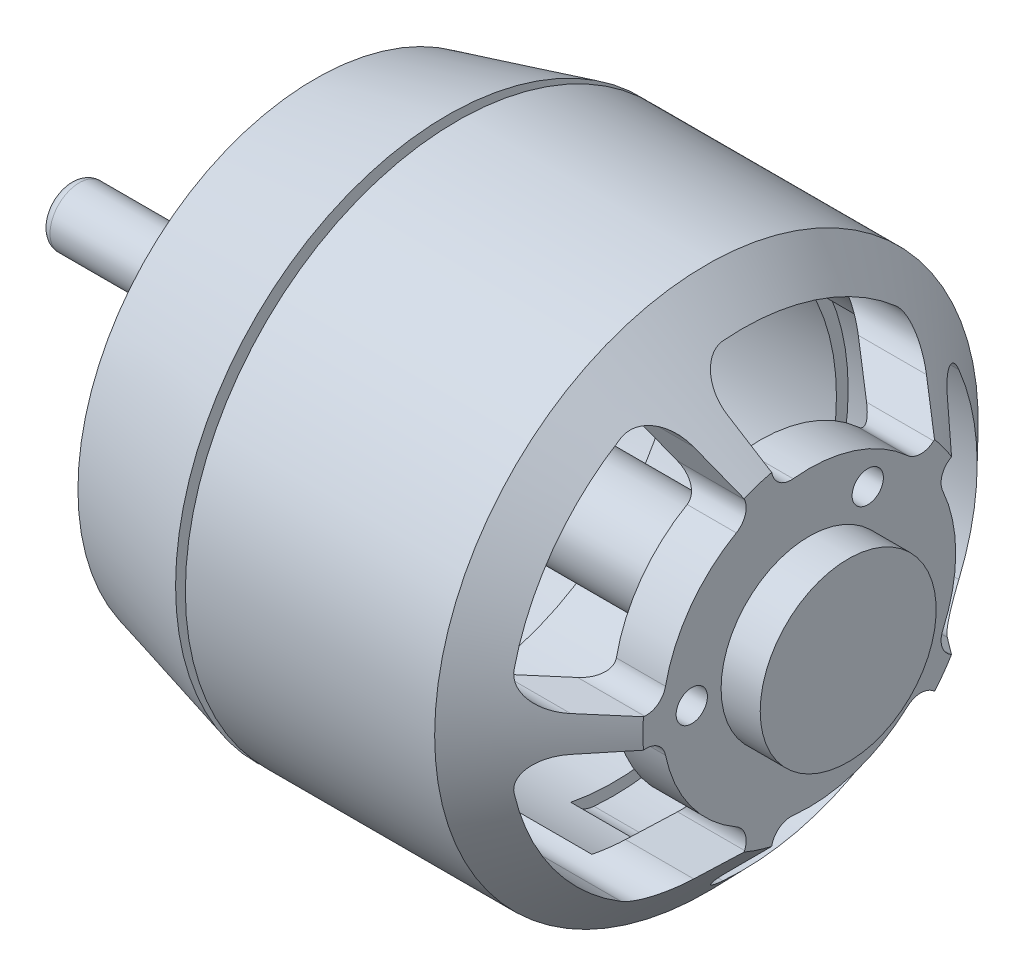
SolidWorks part; units mm, degrees
ref_plane "Front Plane" through (0, 0, 0) normal (0, 0, 1) x (1, 0, 0)
ref_plane "Top Plane" through (0, 0, 0) normal (0, 1, 0) x (1, 0, 0)
ref_plane "Right Plane" through (0, 0, 0) normal (1, 0, 0) x (0, 0, -1)
sketch "Sketch1" plane through (0, 0, 0) normal (0, 1, 0) x (1, 0, 0)
  line L0 (0, 0) -> (27.75, 0)
  line L1 (27.75, 0) -> (27.75, -4.5)
  line L2 (27.75, -4.5) -> (25.75, -4.5)
  line L3 (25.75, -4.5) -> (25.75, -8.5)
  line L4 (7.25, -13.9) -> (0, -12)
  line L5 (7.25, -12.9) -> (2, -11.5241)
  line L6 (7.75, -13.9) -> (20.5, -13.9)
  line L7 (20.5, -13.9) -> (25.75, -8.5)
  line L9 (0, -12) -> (0, -1.5)
  line L10 (7.75, -13.9) -> (7.75, -11.4)
  line L12 (23.25, -2.5) -> (23.25, -7.485)
  line L13 (19.4438, -11.4) -> (23.25, -7.485)
  line L14 (7.75, -11.4) -> (19.4438, -11.4)
  line L17 (2, -2.5) -> (23.25, -2.5)
  line L20 (7.25, -13.9) -> (7.25, -12.9)
  line L21 (2, -2.5) -> (2, -11.5241)
  line L22 (0, 0) -> (-12.07, 0)
  line L23 (-12.07, 0) -> (-12.07, -1.5)
  line L24 (-12.07, -1.5) -> (0, -1.5)
  dimension "D1" = 4.5
  dimension "D2" = 13.9
  dimension "D3" = 27.75
  dimension "D4" = 12.07
  dimension "D5" = 1.5
revolve "Revolve3" add sketch "Sketch1" angle 360 about L0
sketch "Sketch2" plane through (0, 0, 0) normal (1, 0, 0) x (0, 0, -1)
  line L0 (0, 0) -> (10.6066, 10.6066) construction
  line L1 (0, 0) -> (-4.9404, 4.9404) construction
  circle A0 centre (0, 0) radius 9 construction
  circle A1 centre (0, 9) radius 2.5
  circle A2 centre (-9, 0) radius 2.5
  circle A3 centre (9, 0) radius 2.5
  circle A4 centre (0, -9) radius 2.5
  circle A5 centre (0, 0) radius 9.5 construction
  circle A6 centre (0, 0) radius 8 construction
  circle A7 centre (5.6598, 5.6598) radius 1.25
  circle A8 centre (-5.6569, -5.6569) radius 1.25
  circle A9 centre (-6.7175, 6.7175) radius 1.25
  circle A10 centre (6.7175, -6.7175) radius 1.25
extrude "Cut-Extrude4" cut sketch "Sketch2" along normal blind 5 contours A1 | A2 | A9 | A7 | A8 | A4 | A3 | A10 region at (0, 9, 0) region at (0, 0, 9) region at (0, 0, -9) region at (0, -9, 0) region at (0, 5.6598, -5.6598) region at (0, -5.6569, 5.6569) region at (0, 6.7175, 6.7175) region at (0, -6.7175, -6.7175)
sketch "Sketch3" plane through (25.75, 0, 0) normal (1, 0, 0) x (0, 0, -1)
  line L0 (0, 0) -> (3.6969, 6.4032) construction
  line L1 (0, 0) -> (3.7407, -6.479) construction
  line L2 (0, 0) -> (7.3776, 0) construction
  line L3 (6.3705, 5.5378) -> (7.8432, 6.818)
  line L4 (-8.4089, 0.7357) -> (-10.3528, 0.9057)
  line L5 (-3.2982, 7.77) -> (-4.0606, 9.5662)
  line L6 (-1.8988, 8.2246) -> (-2.3378, 10.126)
  line L7 (7.2353, -4.3474) -> (8.9079, -5.3524)
  line L8 (7.2353, 4.3474) -> (8.9079, 5.3524)
  line L9 (-1.8988, -8.2246) -> (-2.3378, -10.126)
  line L10 (6.3705, -5.5378) -> (7.8432, -6.818)
  line L11 (-8.4089, -0.7357) -> (-10.3528, -0.9057)
  line L12 (-3.2982, -7.77) -> (-4.0606, -9.5662)
  circle A0 centre (0, 0) radius 6 construction
  circle A1 centre (-6, 0) radius 0.8
  circle A2 centre (3, 5.1962) radius 0.8
  circle A3 centre (3, -5.1962) radius 0.8
  arc A4 (-3.2982, 7.77) -> (-3.7223, 6.5111) centre (-4.2187, 7.3792) cw
  arc A5 (-8.4089, 0.7357) -> (-7.3427, 1.5281) centre (-8.3217, 1.7319) ccw
  arc A6 (-6.2187, 10.2629) -> (-11.6823, 2.7429) centre (0, 0) ccw
  arc A7 (-3.7223, 6.5111) -> (-7.3427, 1.5281) centre (0, 0) ccw
  arc A8 (-6.2187, 10.2629) -> (-4.0606, 9.5662) centre (-5.4414, 8.9801) cw
  arc A9 (-11.6823, 2.7429) -> (-10.3528, 0.9057) centre (-10.222, 2.4) ccw
  arc A10 (-1.0014, 11.9581) -> (-2.3378, 10.126) centre (-0.8762, 10.4634) ccw
  arc A11 (7.839, 9.0857) -> (-1.0014, 11.9581) centre (0, 0) ccw
  arc A12 (7.839, 9.0857) -> (7.8432, 6.818) centre (6.8591, 7.95) cw
  arc A13 (6.3705, 5.5378) -> (5.0421, 5.5522) centre (5.7144, 6.2925) cw
  arc A14 (5.0421, 5.5522) -> (-0.8157, 7.4555) centre (0, 0) ccw
  arc A15 (-1.8988, 8.2246) -> (-0.8157, 7.4555) centre (-0.9244, 8.4496) ccw
  arc A16 (11.0634, 4.6476) -> (8.9079, 5.3524) centre (9.6805, 4.0667) ccw
  arc A17 (11.0634, -4.6476) -> (11.0634, 4.6476) centre (0, 0) ccw
  arc A18 (11.0634, -4.6476) -> (8.9079, -5.3524) centre (9.6805, -4.0667) cw
  arc A19 (7.2353, -4.3474) -> (6.8386, -3.0796) centre (7.7504, -3.4903) cw
  arc A20 (6.8386, -3.0796) -> (6.8386, 3.0796) centre (0, 0) ccw
  arc A21 (7.2353, 4.3474) -> (6.8386, 3.0796) centre (7.7504, 3.4903) ccw
  arc A22 (7.839, -9.0857) -> (7.8432, -6.818) centre (6.8591, -7.95) ccw
  arc A23 (-1.0014, -11.9581) -> (7.839, -9.0857) centre (0, 0) ccw
  arc A24 (-1.0014, -11.9581) -> (-2.3378, -10.126) centre (-0.8762, -10.4634) cw
  arc A25 (-1.8988, -8.2246) -> (-0.8157, -7.4555) centre (-0.9244, -8.4496) cw
  arc A26 (-0.8157, -7.4555) -> (5.0421, -5.5522) centre (0, 0) ccw
  arc A27 (6.3705, -5.5378) -> (5.0421, -5.5522) centre (5.7144, -6.2925) ccw
  arc A28 (-6.2187, -10.2629) -> (-4.0606, -9.5662) centre (-5.4414, -8.9801) ccw
  arc A29 (-11.6823, -2.7429) -> (-6.2187, -10.2629) centre (0, 0) ccw
  arc A30 (-11.6823, -2.7429) -> (-10.3528, -0.9057) centre (-10.222, -2.4) cw
  arc A31 (-8.4089, -0.7357) -> (-7.3427, -1.5281) centre (-8.3217, -1.7319) cw
  arc A32 (-7.3427, -1.5281) -> (-3.7223, -6.5111) centre (0, 0) ccw
  arc A33 (-3.2982, -7.77) -> (-3.7223, -6.5111) centre (-4.2187, -7.3792) ccw
  point P78 (0, 0)
  dimension "D1" = 1
  dimension "D2" = 1.5
  dimension "D3" = 5
extrude "Cut-Extrude5" cut sketch "Sketch3" against normal blind 10
fillet "Fillet1" radius 0.5 1 edges at (-12.07, 0, 1.5)
chamfer "Chamfer1" distance 0.5 angle 45 1 edges at (0, 0, 12) first distance on face at (7.25, 0, 13.9)
